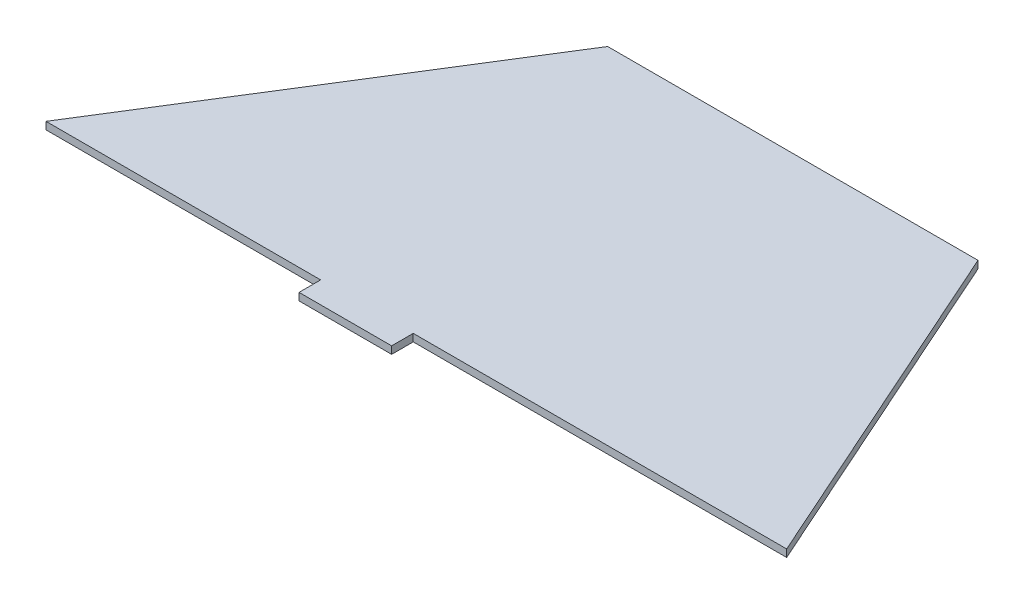
SolidWorks part; units mm, degrees
ref_plane "Front Plane" through (0, 0, 0) normal (0, 0, 1) x (1, 0, 0)
ref_plane "Top Plane" through (0, 0, 0) normal (0, 1, 0) x (1, 0, 0)
ref_plane "Right Plane" through (0, 0, 0) normal (1, 0, 0) x (0, 0, -1)
sketch "Sketch1" plane through (0, 0, 0) normal (0, 1, 0) x (1, 0, 0)
  line L0 (0, 0) -> (88.9, 142.24)
  line L1 (88.9, 142.24) -> (241.3, 142.24)
  line L2 (241.3, 142.24) -> (304.8, 0)
  line L4 (0, 0) -> (113.03, 0)
  line L5 (113.03, 0) -> (113.03, -8.89)
  line L6 (113.03, -8.89) -> (151.13, -8.89)
  line L7 (151.13, -8.89) -> (151.13, 0)
  line L8 (151.13, 0) -> (304.8, 0)
  dimension "D1" = 142.24
  dimension "D2" = 304.8
  dimension "D3" = 152.4
  dimension "D4" = 88.9
  dimension "D5" = 8.89
  dimension "D6" = 38.1
  dimension "D7" = 153.67
  dimension "D8" = 142.24
extrude "Boss-Extrude1" add sketch "Sketch1" along normal blind 3.048
